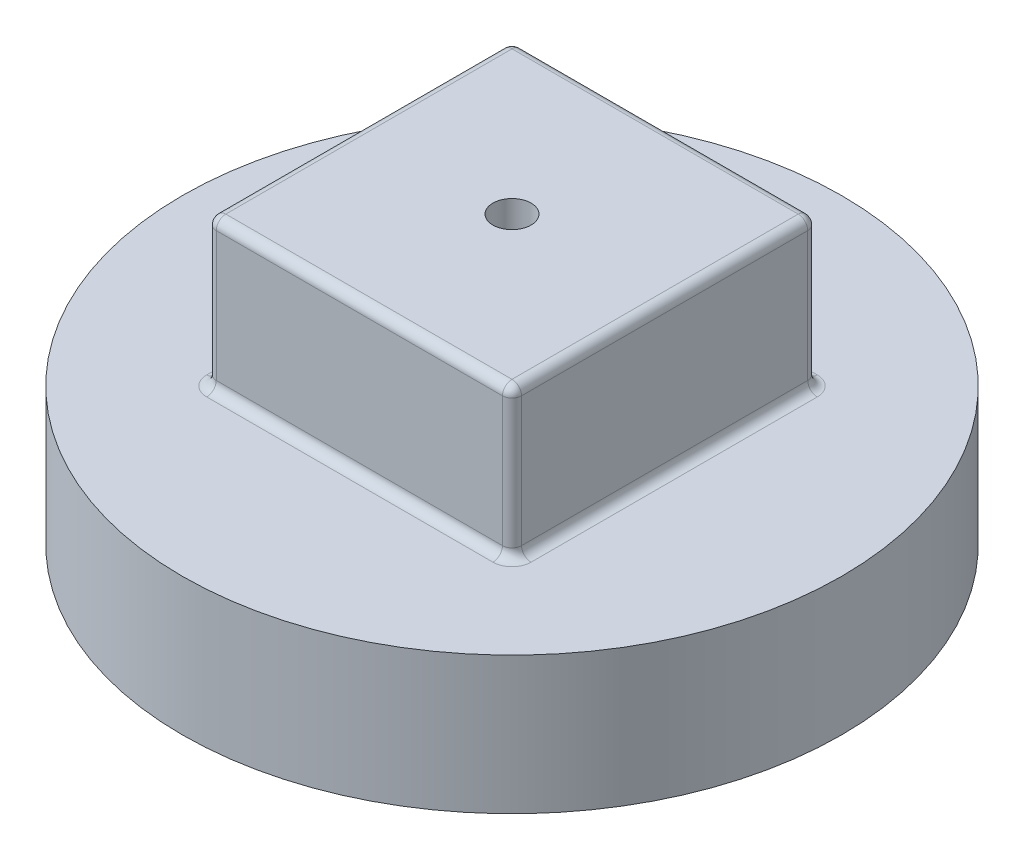
SolidWorks part; units mm, degrees
ref_plane "Front Plane" through (0, 0, 0) normal (0, 0, 1) x (1, 0, 0)
ref_plane "Top Plane" through (0, 0, 0) normal (0, 1, 0) x (1, 0, 0)
ref_plane "Right Plane" through (0, 0, 0) normal (1, 0, 0) x (0, 0, -1)
sketch "Sketch1" plane through (0, 0, 0) normal (0, 0, 1) x (1, 0, 0)
  line L0 (0, -987.3117) -> (0, 49012.6883) construction
  line L1 (0, 0) -> (54.864, 0)
  line L2 (54.864, 0) -> (54.864, -22.86)
  line L3 (54.864, -22.86) -> (49.784, -22.86)
  line L4 (49.784, -22.86) -> (49.784, -6.731)
  line L5 (49.784, -6.731) -> (0, -6.731)
  line L6 (0, -6.731) -> (0, 0)
  line L7 (55, 0) -> (-55, 0) construction
  dimension "D1" = 109.728
  dimension "D2" = 99.568
  dimension "D3" = 22.86
  dimension "D4" = 16.129
revolve "Revolve1" add sketch "Sketch1" angle 360 about L0
sketch "Sketch2" plane through (0, 0, 0) normal (0, 1, 0) x (1, 0, 0)
  line L1 (25.4, -25.4) -> (-25.4, -25.4)
  line L2 (25.4, -25.4) -> (25.4, 25.4)
  line L3 (25.4, 25.4) -> (-25.4, 25.4)
  line L4 (-25.4, -25.4) -> (-25.4, 25.4)
  line L5 (25.4, -25.4) -> (-25.4, 25.4) construction
  line L6 (25.4, 25.4) -> (-25.4, -25.4) construction
  point P0 (0, 0)
  dimension "D1" = 50.8
extrude "Boss-Extrude1" add sketch "Sketch2" along normal blind 24.765
shell "Shell1" thickness 6.35 removed face at (0, -6.731, -49.784)
fillet "Fillet1" radius 1.5875 4 edges at (25.4, 12.3825, -25.4) (25.4, 12.3825, 25.4) (-25.4, 12.3825, 25.4) (-25.4, 12.3825, -25.4)
fillet "Fillet2" radius 1.5875 16 edges at (-24.935, 0, 24.935) (-25.4, 0, 0) (-24.935, 0, -24.935) (0, 0, -25.4) (24.935, 0, -24.935) (25.4, 0, 0) (24.935, 0, 24.935) (-24.935, 24.765, 24.935) (-25.4, 24.765, 0) (-24.935, 24.765, -24.935) (0, 24.765, -25.4) (24.935, 24.765, -24.935) (25.4, 24.765, 0) (24.935, 24.765, 24.935) (0, 0, 25.4) (0, 24.765, 25.4)
sketch "Sketch3" plane through (0, 0, 0) normal (0, 1, 0) x (1, 0, 0)
  circle A0 centre (0, 0) radius 3.175
  dimension "D1" = 6.35
extrude "Cut-Extrude1" cut sketch "Sketch3" against normal through all and the other way through all
